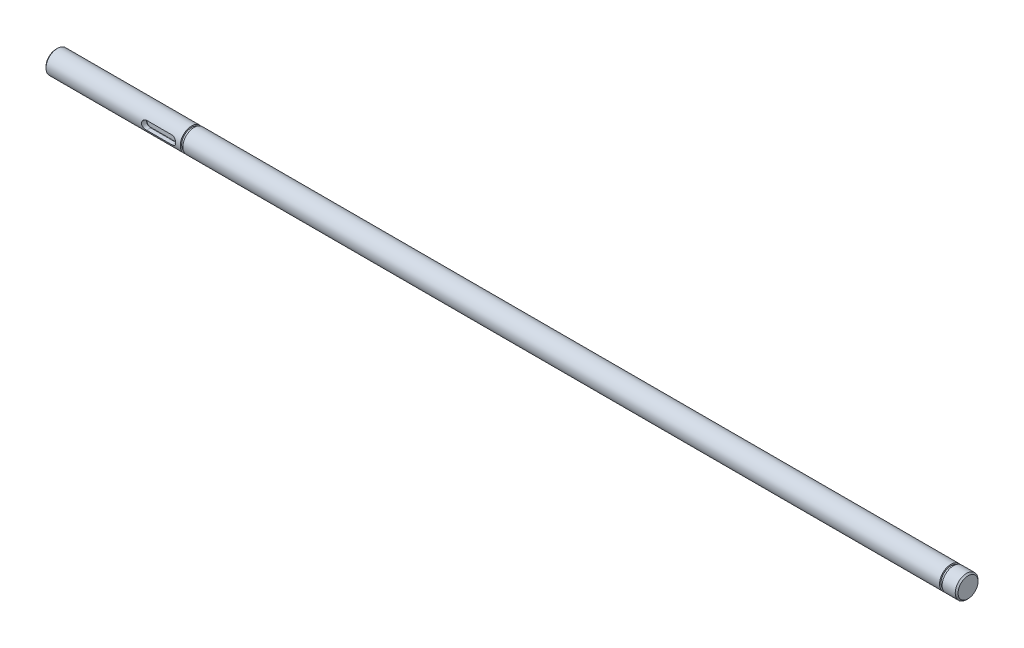
SolidWorks part; units mm, degrees
ref_plane "Front Plane" through (0, 0, 0) normal (0, 0, 1) x (1, 0, 0)
ref_plane "Top Plane" through (0, 0, 0) normal (0, 1, 0) x (1, 0, 0)
ref_plane "Right Plane" through (0, 0, 0) normal (1, 0, 0) x (0, 0, -1)
sketch "Sketch1" plane through (0, 0, 0) normal (0, 0, 1) x (1, 0, 0)
  line L0 (0, 0) -> (320, 0) construction
  line L1 (0, 0) -> (320, 0)
  line L2 (320, 0) -> (320, 4)
  line L3 (320, 4) -> (0, 4)
  line L4 (0, 4) -> (0, 0)
  dimension "L" = 320
  dimension "D" = 8
revolve "Revolve1" add sketch "Sketch1" angle 360 about L0
chamfer "Chamfer1" distance 0.5 angle 45 2 edges at (320, 0, 4) (0, 0, 4)
ref_plane "Plane1" through (0, 0, 4) normal (0, 0, 1) x (1, 0, 0)
ref_plane "Plane2" through (320, 0, 0) normal (1, 0, 0) x (0, 0, -1)
other "DeleteFace1" [suppressed]
chamfer "Chamfer2" [suppressed] distance 2 angle 45
ref_plane "Dim. KC" through (34, 0, 0) normal (1, 0, 0) x (0, 0, -1)
ref_plane "Plane3" through (34, 0, 0) normal (1, 0, 0) x (0, 0, -1)
ref_plane "Plane4" through (46, 0, 0) normal (1, 0, 0) x (0, 0, -1)
sketch "Sketch2" plane through (0, 0, 4) normal (0, 0, 1) x (1, 0, 0)
  line L0 (34, 0) -> (46, 0) construction
  line L1 (34, 1.5) -> (46, 1.5)
  line L2 (34, 1.5) -> (34, -1.5) construction
  line L3 (34, -1.5) -> (46, -1.5)
  line L4 (46, 1.5) -> (46, -1.5) construction
  line L5 (40, 1.5) -> (40, -1.5) construction
  line L6 (34, -4.4) -> (34, 4.4) construction
  line L7 (46, 1.5) -> (46, -1.5)
  line L8 (46, -4.4) -> (46, 4.4) construction
  line L9 (34, 1.5) -> (34, -1.5)
  line L12 (34, -4.4) -> (34, 4.4) construction
  dimension "A" = 12
  dimension "B_s" = 3
extrude "Boss-Extrude1" add sketch "Sketch2" against normal blind 1.8 separate body
fillet "Fillet1" 2 edges at (34, 1.5, 3.1) (34, -1.5, 3.1) type full round first side face at (40, 1.5, 3.1) second side face at (40, -1.5, 3.1) middle face at (34, 0, 3.1)
fillet "Fillet2" 2 edges at (46, 1.5, 3.1) (46, -1.5, 3.1) type full round first side face at (40.75, 1.5, 3.1) second side face at (40.75, -1.5, 3.1) middle face at (46, 0, 3.1)
sketch "Sketch3" plane through (0, 0, 4) normal (0, 0, 1) x (1, 0, 0)
  line L0 (47, 1.5) -> (47, -1.5) construction
  line L1 (44.5, 1.5) -> (49.5, 1.5)
  line L2 (44.5, 1.5) -> (44.5, -1.5)
  line L3 (44.5, -1.5) -> (49.5, -1.5)
  line L4 (49.5, 1.5) -> (49.5, -1.5)
  line L7 (44.5, 0) -> (49.5, 0) construction
  line L9 (48, 1.5) -> (48, -1.5) construction
  line L10 (46, 1.5) -> (46, -1.5) construction
  line L11 (34, 1.5) -> (46, 1.5) construction
  line L12 (34, -1.5) -> (46, -1.5) construction
  dimension "D1" = 1.5
  dimension "D2" = 2
  dimension "D3" = 1.5
extrude "Boss-Extrude2" [suppressed] add sketch "Sketch3" against normal blind 1.8
fillet "Fillet3" radius 0.1 4 edges at (40, -1.5, 2.2) (46, 0, 2.2) (40, 1.5, 2.2) (34, 0, 2.2)
other "DeleteFace2" [suppressed]
other "DeleteFace3" [suppressed]
combine bodies "Combine1" operation type subtract main body 101 bodies to subtract 132
ref_plane "KC_SEC1" through (40, 0, 0) normal (1, 0, 0) x (0, 0, -1)
ref_plane "KC_SEC2" through (47, 0, 0) normal (1, 0, 0) x (0, 0, -1)
ref_plane "Dim. WKC" [suppressed] through (2, 0, 0) normal (1, 0, 0) x (0, 0, -1)
ref_plane "Dim. K" [suppressed] through (20, 0, 0) normal (1, 0, 0) x (0, 0, -1)
ref_plane "Plane5" [suppressed] through (2, 0, 0) normal (1, 0, 0) x (0, 0, -1)
ref_plane "Plane6" [suppressed] through (20, 0, 0) normal (1, 0, 0) x (0, 0, -1)
sketch "Sketch4" [suppressed] plane through (0, 0, 4) normal (0, 0, 1) x (1, 0, 0)
  line L0 (2, 1.5) -> (2, -1.5)
  line L1 (2, 1.5) -> (8, 1.5)
  line L2 (2, 1.5) -> (2, -1.5) construction
  line L3 (2, -1.5) -> (8, -1.5)
  line L4 (8, 1.5) -> (8, -1.5)
  line L5 (2, -4.4) -> (2, 4.4) construction
  line L6 (2, -3.3) -> (2, 3.3) construction
  line L7 (8, 0) -> (2, 0) construction
  line L8 (5, 1.5) -> (5, -1.5) construction
  dimension "B_s" = 3
  dimension "C" = 6
extrude "Boss-Extrude3" [suppressed] add sketch "Sketch4" against normal blind 1.8 separate body
sketch "Sketch5" [suppressed] plane through (0, 0, 4) normal (0, 0, 1) x (1, 0, 0)
  line L0 (0, 0) -> (20, 0) construction
  line L2 (20, -3.3) -> (20, 3.3) construction
  line L4 (20, -3.3) -> (20, 3.3) construction
  line L5 (17, 1.5) -> (17, -1.5) construction
  line L9 (14, 1.5) -> (20, 1.5)
  line L10 (14, 1.5) -> (14, -1.5)
  line L11 (14, -1.5) -> (20, -1.5)
  line L12 (20, 1.5) -> (20, -1.5) construction
  line L13 (20, 1.5) -> (20, -1.5)
  dimension "B_s" = 3
  dimension "E" = 6
extrude "Boss-Extrude4" [suppressed] add sketch "Sketch5" against normal blind 1.8 separate body
sketch "Sketch6" [suppressed] plane through (0, 0, 4) normal (0, 0, 1) x (1, 0, 0)
  line L0 (2, 1.5) -> (8, 1.5) construction
  line L1 (6.5, 1.5) -> (11.5, 1.5)
  line L2 (6.5, 1.5) -> (6.5, -1.5)
  line L3 (6.5, -1.5) -> (11.5, -1.5)
  line L4 (11.5, 1.5) -> (11.5, -1.5)
  line L5 (2, -1.5) -> (8, -1.5) construction
  line L6 (8, 1.5) -> (8, -1.5) construction
  line L7 (9, 1.5) -> (9, -1.5) construction
  line L8 (10, 1.5) -> (10, -1.5) construction
  dimension "D1" = 1.5
  dimension "D2" = 2
  dimension "D3" = 1.5
extrude "Boss-Extrude5" [suppressed] add sketch "Sketch6" against normal blind 1.8
fillet "Fillet4" [suppressed] type full round
fillet "Fillet5" [suppressed] type full round
fillet "Fillet6" [suppressed] radius 0.1
fillet "Fillet7" [suppressed] type full round
fillet "Fillet8" [suppressed] type full round
fillet "Fillet9" [suppressed] radius 0.1
other "DeleteFace4" [suppressed]
other "DeleteFace5" [suppressed]
other "DeleteFace6" [suppressed]
other "DeleteFace7" [suppressed]
combine bodies "Combine2" [suppressed] operation type subtract main body 101 bodies to subtract 149 135
ref_plane "WKC_SEC1" [suppressed] through (5, 0, 0) normal (1, 0, 0) x (0, 0, -1)
ref_plane "WKC_SEC2" [suppressed] through (17, 0, 0) normal (1, 0, 0) x (0, 0, -1)
ref_plane "WKC_SEC3" [suppressed] through (9, 0, 0) normal (1, 0, 0) x (0, 0, -1)
ref_plane "Dim. KZ" [suppressed] through (2, 0, 0) normal (1, 0, 0) x (0, 0, -1)
ref_plane "Plane7" [suppressed] through (2, 0, 0) normal (1, 0, 0) x (0, 0, -1)
ref_plane "Plane8" [suppressed] through (8, 0, 0) normal (1, 0, 0) x (0, 0, -1)
sketch "Sketch7" [suppressed] plane through (0, 0, 4) normal (0, 0, 1) x (1, 0, 0)
  line L0 (0, 0) -> (8, 0) construction
  line L1 (2, 1.5) -> (8, 1.5)
  line L2 (2, 1.5) -> (2, -1.5) construction
  line L3 (2, -1.5) -> (8, -1.5)
  line L4 (8, 1.5) -> (8, -1.5) construction
  line L5 (2, -4.4) -> (2, 4.4) construction
  line L6 (2, -4.4) -> (2, 4.4) construction
  line L7 (2, 1.5) -> (2, -1.5)
  line L8 (8, 1.5) -> (8, -1.5)
  line L9 (8, -4.4) -> (8, 4.4) construction
  line L10 (5, 1.5) -> (5, -1.5) construction
  dimension "B_s" = 3
  dimension "Z" = 6
extrude "Boss-Extrude6" [suppressed] add sketch "Sketch7" against normal blind 1.8 separate body
fillet "Fillet10" [suppressed] type full round
fillet "Fillet11" [suppressed] type full round
sketch "Sketch8" [suppressed] plane through (0, 0, 4) normal (0, 0, 1) x (1, 0, 0)
  line L0 (1, 1.5) -> (1, -1.5) construction
  line L1 (-1.5, 1.5) -> (3.5, 1.5)
  line L2 (-1.5, 1.5) -> (-1.5, -1.5)
  line L3 (-1.5, -1.5) -> (3.5, -1.5)
  line L4 (3.5, 1.5) -> (3.5, -1.5)
  line L5 (2, 1.5) -> (2, -1.5) construction
  line L7 (-1.5, 0) -> (3.5, 0) construction
  line L9 (0, 1.5) -> (0, -1.5) construction
  line L10 (2, 1.5) -> (8, 1.5) construction
  line L11 (2, -1.5) -> (8, -1.5) construction
  dimension "D1" = 1.5
  dimension "D2" = 2
  dimension "D3" = 1.5
extrude "Boss-Extrude7" [suppressed] add sketch "Sketch8" against normal blind 1.8
fillet "Fillet12" [suppressed] radius 0.1
other "DeleteFace8" [suppressed]
other "DeleteFace9" [suppressed]
combine bodies "Combine3" [suppressed] operation type subtract main body 101 bodies to subtract 147
ref_plane "KZ_SEC1" [suppressed] through (5, 0, 0) normal (1, 0, 0) x (0, 0, -1)
ref_plane "KZ_SEC2" [suppressed] through (1, 0, 0) normal (1, 0, 0) x (0, 0, -1)
ref_plane "Dim. FC" [suppressed] through (1, 0, 0) normal (1, 0, 0) x (0, 0, -1)
sketch "Sketch9" [suppressed] plane through (0, 0, 0) normal (0, 1, 0) x (1, 0, 0)
  line L0 (0, 0) -> (2, 0) construction
  line L1 (1, -3) -> (2, -3)
  line L2 (1, -3) -> (1, -4)
  line L3 (1, -4) -> (2, -4)
  line L4 (2, -3) -> (2, -4)
  line L5 (1, -3.3) -> (1, 3.3) construction
  line L6 (1.5, -4) -> (1.5, -3) construction
  dimension "G" = 2
  dimension "H" = 1
  dimension "D" = 8
extrude "Cut-Extrude1" [suppressed] cut sketch "Sketch9" against normal through all and the other way through all
ref_plane "FC_SEC" [suppressed] through (1.5, 0, 0) normal (1, 0, 0) x (0, 0, -1)
ref_plane "Dim. WFC" [suppressed] through (1, 0, 0) normal (1, 0, 0) x (0, 0, -1)
ref_plane "Dim. W" [suppressed] through (19, 0, 0) normal (1, 0, 0) x (0, 0, -1)
sketch "Sketch10" [suppressed] plane through (0, 0, 0) normal (0, 1, 0) x (1, 0, 0)
  line L0 (0, 0) -> (19, 0) construction
  line L1 (1, -4) -> (2, -4)
  line L2 (1, -4) -> (1, -3)
  line L3 (1, -3) -> (2, -3)
  line L4 (2, -4) -> (2, -3)
  line L5 (1.5, -3) -> (1.5, -4) construction
  line L6 (19, -4) -> (18, -4)
  line L7 (19, -4) -> (19, -3)
  line L8 (19, -3) -> (18, -3)
  line L9 (18, -4) -> (18, -3)
  line L10 (1, -3.3) -> (1, 3.3) construction
  line L11 (19, -3.3) -> (19, 3.3) construction
  line L12 (18.5, -3) -> (18.5, -4) construction
  dimension "J" = 2
  dimension "V" = 2
  dimension "H" = 1
  dimension "D" = 8
  dimension "H_s_R" = 1
extrude "Cut-Extrude2" [suppressed] cut sketch "Sketch10" against normal through all and the other way through all
ref_plane "WFC_SEC1" [suppressed] through (1.5, 0, 0) normal (1, 0, 0) x (0, 0, -1)
ref_plane "WFC_SEC2" [suppressed] through (18.5, 0, 0) normal (1, 0, 0) x (0, 0, -1)
ref_plane "Dim. SFC" [suppressed] through (1, 0, 0) normal (1, 0, 0) x (0, 0, -1)
sketch "Sketch11" [suppressed] plane through (0, 0, 0) normal (0, 1, 0) x (1, 0, 0)
  line L0 (0, 0) -> (2, 0) construction
  line L1 (1, -4) -> (2, -4)
  line L2 (1, -4) -> (1, -3)
  line L3 (1, -3) -> (2, -3)
  line L4 (2, -4) -> (2, -3)
  line L5 (1, -3.3) -> (1, 3.3) construction
  line L6 (1.5, -3) -> (1.5, -4) construction
  dimension "D" = 8
  dimension "SG" = 1
  dimension "H" = 1
extrude "Cut-Extrude3" [suppressed] cut sketch "Sketch11" against normal through all and the other way through all
pattern_circular "CirPattern1" [suppressed] count 2 every 120 of bodies 119
ref_plane "Plane9" [suppressed] through (0, 0, 0) normal (0, -0.5, 0.866) x (1, 0, 0)
sketch "Sketch12" [suppressed] plane through (0, 0, 0) normal (0, -0.5, 0.866) x (1, 0, 0)
  line L0 (0, 0) -> (2, 0) construction
  line L2 (1, -3) -> (2, -3)
  line L3 (1, -3) -> (1, -4)
  line L4 (1, -4) -> (2, -4)
  line L5 (2, -3) -> (2, -4)
  line L6 (1, -3.3) -> (1, 3.3) construction
  dimension "D" = 8
  dimension "SG" = 1
  dimension "H" = 1
ref_plane "SFC_SEC" [suppressed] through (1.5, 0, 0) normal (1, 0, 0) x (0, 0, -1)
sketch "Sketch13" [suppressed] plane through (1.5, 0, 0) normal (1, 0, 0) x (0, 0, -1)
  line L0 (-4, 0) -> (-3, 0) construction
  line L1 (-3, 0) -> (-4, 0) construction
  line L2 (2, -3.4641) -> (1.5, -2.5981) construction
  line L3 (1.5, -2.5981) -> (2, -3.4641) construction
  line L4 (1.5, -2.5981) -> (2, -3.4641) construction
  dimension "ANG" = 120
sketch "Sketch14" [suppressed] plane through (0, 0, 0) normal (0, 1, 0) x (1, 0, 0)
  line L0 (0, 0) -> (20, 0) construction
  line L1 (1.5, 4) -> (1.5, 3.5) construction
  line L2 (0, 3.5) -> (3, 3.5)
  line L3 (0, 3.5) -> (0, 4)
  line L4 (0, 4) -> (3, 4)
  line L5 (3, 3.5) -> (3, 4)
  line L6 (17, 3.5) -> (20, 3.5)
  line L7 (17, 3.5) -> (17, 4)
  line L8 (17, 4) -> (20, 4)
  line L9 (20, 3.5) -> (20, 4)
  line L10 (0, -4) -> (3, -4)
  line L11 (0, -4) -> (0, -3.5)
  line L12 (0, -3.5) -> (3, -3.5)
  line L13 (3, -4) -> (3, -3.5)
  line L14 (17, -4) -> (20, -4)
  line L15 (17, -4) -> (17, -3.5)
  line L16 (17, -3.5) -> (20, -3.5)
  line L17 (20, -4) -> (20, -3.5)
  line L18 (1.5, -3.5) -> (1.5, -4) construction
  line L19 (18.5, 4) -> (18.5, 3.5) construction
  line L20 (18.5, -3.5) -> (18.5, -4) construction
  dimension "D" = 8
  dimension "W_1" = 4
  dimension "KWC" = 3
  dimension "KWC_L1" = 3
  dimension "KWC_R1" = 3
  dimension "KWC_R2" = 3
  dimension "W_1_R" = 7
extrude "Cut-Extrude4" [suppressed] cut sketch "Sketch14" against normal through all and the other way through all
ref_plane "KWC_SEC1" [suppressed] through (1.5, 0, 0) normal (1, 0, 0) x (0, 0, -1)
ref_plane "KWC_SEC2" [suppressed] through (18.5, 0, 0) normal (1, 0, 0) x (0, 0, -1)
sketch "Sketch15" [suppressed] plane through (0, 0, 0) normal (0, 1, 0) x (1, 0, 0)
  line L0 (0, 0) -> (20, 0) construction
  line L1 (1.5, -3) -> (1.5, -4) construction
  line L2 (0, 3) -> (3, 3)
  line L3 (0, 3) -> (0, 4)
  line L4 (0, 4) -> (3, 4)
  line L5 (3, 3) -> (3, 4)
  line L6 (17, 3) -> (20, 3)
  line L7 (17, 3) -> (17, 4)
  line L8 (17, 4) -> (20, 4)
  line L9 (20, 3) -> (20, 4)
  line L10 (0, -4) -> (3, -4)
  line L11 (0, -4) -> (0, -3)
  line L12 (0, -3) -> (3, -3)
  line L13 (3, -4) -> (3, -3)
  line L14 (17, -4) -> (20, -4)
  line L15 (17, -4) -> (17, -3)
  line L16 (17, -3) -> (20, -3)
  line L17 (20, -4) -> (20, -3)
  line L18 (18.5, -3) -> (18.5, -4) construction
  dimension "D" = 8
  dimension "KWC_L1" = 3
  dimension "KWC_R1" = 3
  dimension "WC" = 6
  dimension "KWC" = 3
  dimension "KWC_R2" = 3
  dimension "WC_R" = 6
extrude "Cut-Extrude5" [suppressed] cut sketch "Sketch15" against normal through all and the other way through all
ref_plane "WC_SEC1" [suppressed] through (1.5, 0, 0) normal (1, 0, 0) x (0, 0, -1)
ref_plane "WC_SEC2" [suppressed] through (18.5, 0, 0) normal (1, 0, 0) x (0, 0, -1)
sketch "Sketch16" plane through (0, 0, 0) normal (0, 0, 1) x (1, 0, 0)
  line L0 (320, 4) -> (0, 4) construction
  line L1 (47.6, 3.5) -> (48.5, 3.5)
  line L2 (47.6, 3.5) -> (47.6, 4)
  line L3 (47.6, 4) -> (48.5, 4)
  line L4 (48.5, 3.5) -> (48.5, 4)
  line L5 (0, 0) -> (48.5, 0) construction
  line L6 (0, 4) -> (0, 0) construction
  dimension "D_s_1" = 7
  dimension "M_s" = 0.9
  dimension "TA" = 48.5
revolve "Cut-Revolve1" cut sketch "Sketch16" angle 360 about L5
sketch "Sketch17" plane through (0, 0, 0) normal (0, 0, 1) x (1, 0, 0)
  line L1 (314, 3.5) -> (314.9, 3.5)
  line L2 (314, 3.5) -> (314, 4)
  line L3 (314, 4) -> (314.9, 4)
  line L4 (314.9, 3.5) -> (314.9, 4)
  line L5 (0, 0) -> (320, 0) construction
  line L7 (320, -3.3) -> (320, 3.3) construction
  dimension "D_s_1" = 7
  dimension "M_s" = 0.9
  dimension "D" = 8
  dimension "TB" = 6
revolve "Cut-Revolve2" cut sketch "Sketch17" angle 360 about L5
sketch "Sketch18" [suppressed] plane through (0, 0, 0) normal (0, 0, 1) x (1, 0, 0)
  line L0 (0, 0) -> (20, 0) construction
  line L1 (0, 4) -> (0, -4) construction
  line L3 (1, 4) -> (5, 4)
  line L4 (1, 4) -> (1, 3.5)
  line L5 (1, 3.5) -> (5, 3.5)
  line L6 (5, 4) -> (5, 3.5)
  line L7 (20, 4) -> (0, 4) construction
  line L8 (20, -3.3) -> (20, 3.3) construction
  dimension "D_s_2" = 7
  dimension "UC" = 1
  dimension "L1_s" = 4
revolve "Cut-Revolve3" [suppressed] cut sketch "Sketch18" angle 360 about L0
ref_plane "Dim. SC" [suppressed] through (2, 0, 0) normal (1, 0, 0) x (0, 0, -1)
sketch "Sketch19" [suppressed] plane through (0, 0, 0) normal (0, 1, 0) x (1, 0, 0)
  line L0 (20, -3.3) -> (20, 3.3) construction
  line L1 (2, -3.5) -> (10, -3.5)
  line L2 (2, -3.5) -> (2, -4)
  line L3 (2, -4) -> (10, -4)
  line L4 (10, -3.5) -> (10, -4)
  line L5 (2, 4) -> (10, 4)
  line L6 (2, 4) -> (2, 3.5)
  line L7 (2, 3.5) -> (10, 3.5)
  line L8 (10, 4) -> (10, 3.5)
  line L9 (6, 4) -> (6, 3.5) construction
  line L10 (6, -3.5) -> (6, -4) construction
  line L12 (0, 0) -> (20, 0) construction
  line L14 (2, -3.3) -> (2, 3.3) construction
  dimension "W_2" = 4
  dimension "L2_s" = 8
  dimension "D" = 8
  dimension "L2_s_L1" = 8
extrude "Cut-Extrude6" [suppressed] cut sketch "Sketch19" against normal through all and the other way through all
ref_plane "SC_SEC" [suppressed] through (6, 0, 0) normal (1, 0, 0) x (0, 0, -1)
equation "\"Plane dim\"= \"D@Sketch1\" * 0.5"
equation "\"D1@Plane3\"= if ( \"KC@Dim. KC\" < 1 , 0 , \"KC@Dim. KC\" )"
equation "\"D1@Plane4\" = if ( \"KC@Dim. KC\" > \"L@Sketch1\" - \"A@Sketch2\" - 1 , \"L@Sketch1\" , \"KC@Dim. KC\" + \"A@Sketch2\" )"
equation "\"D1@Plane5\"=if ( \"WKC@Dim. WKC\" < 1 , 0 , \"WKC@Dim. WKC\" )"
equation "\"D1@Plane6\"=if ( \"K@Dim. K\" < 1 , 0 , \"K@Dim. K\" )"
equation "\"D1@Plane7\"=if ( \"KZ@Dim. KZ\" < 1 , 0 , \"KZ@Dim. KZ\" )"
equation "\"D1@Plane8\"=if ( \"KZ@Dim. KZ\" > \"L@Sketch1\" - \"Z@Sketch7\" - 1 , \"L@Sketch1\", \"KZ@Dim. KZ\" + \"Z@Sketch7\" )"
equation "\"D1@Sketch3\"=\"B_s@Sketch2\"/2"
equation "\"D3@Sketch3\"=\"B_s@Sketch2\"/2"
equation "\"D1@Sketch8\"=\"B_s@Sketch7\"/2"
equation "\"D3@Sketch8\"=\"B_s@Sketch7\"/2"
equation "\"D1@Sketch6\"=\"B_s@Sketch4\"/2"
equation "\"D3@Sketch6\"=\"B_s@Sketch4\"/2"
equation "\"D@Sketch12\" = \"D@Sketch11\""
equation "\"SG@Sketch12\" = \"SG@Sketch11\""
equation "\"H@Sketch12\"= \"H@Sketch11\""
